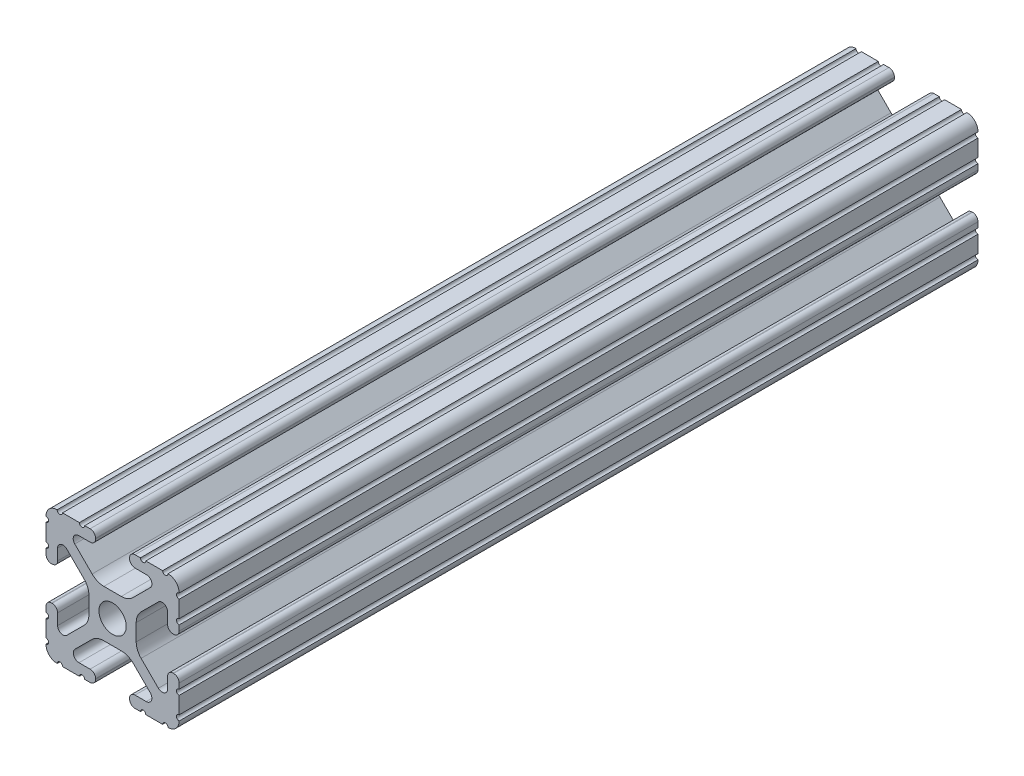
SolidWorks part; units mm, degrees
ref_plane "Front Plane" through (0, 0, 0) normal (0, 0, 1) x (1, 0, 0)
ref_plane "Top Plane" through (0, 0, 0) normal (0, 1, 0) x (1, 0, 0)
ref_plane "Right Plane" through (0, 0, 0) normal (1, 0, 0) x (0, 0, -1)
sketch "Sketch1" plane through (0, 0, 0) normal (0, 0, 1) x (1, 0, 0)
  line L88 (-7.1797, -8.6452) -> (-3.9523, -5.4237)
  line L89 (-1.7093, -4.4958) -> (1.7093, -4.4958)
  line L90 (3.9523, -5.4237) -> (7.1797, -8.6452)
  line L91 (6.4164, -10.4902) -> (4.2875, -10.4902)
  line L92 (3.2385, -11.5392) -> (3.2385, -11.651)
  line L93 (4.2875, -12.7) -> (5.3171, -12.7)
  line L94 (6.3331, -12.7) -> (9.5504, -12.7)
  line L95 (12.7, -9.5504) -> (12.7, -6.3331)
  line L96 (12.7, -5.3171) -> (12.7, -4.2875)
  line L97 (11.651, -3.2385) -> (11.5392, -3.2385)
  line L98 (10.4902, -4.2875) -> (10.4902, -6.4021)
  line L99 (8.7371, -7.1294) -> (5.441, -3.8408)
  line L100 (4.5085, -1.5932) -> (4.5085, 1.5932)
  line L101 (5.441, 3.8408) -> (8.7371, 7.1294)
  line L102 (10.4902, 6.4021) -> (10.4902, 4.2875)
  line L103 (11.5392, 3.2385) -> (11.651, 3.2385)
  line L104 (12.7, 4.2875) -> (12.7, 5.3171)
  line L105 (12.7, 6.3331) -> (12.7, 9.5504)
  line L106 (9.5504, 12.7) -> (6.3331, 12.7)
  line L107 (5.3171, 12.7) -> (4.2875, 12.7)
  line L108 (3.2385, 11.651) -> (3.2385, 11.5392)
  line L109 (4.2875, 10.4902) -> (6.4768, 10.4902)
  line L110 (7.207, 8.7244) -> (3.8983, 5.4232)
  line L111 (1.6558, 4.4958) -> (-1.6558, 4.4958)
  line L112 (-3.8983, 5.4232) -> (-7.207, 8.7244)
  line L113 (-6.4768, 10.4902) -> (-4.2875, 10.4902)
  line L114 (-3.2385, 11.5392) -> (-3.2385, 11.651)
  line L115 (-4.2875, 12.7) -> (-5.3171, 12.7)
  line L116 (-6.3331, 12.7) -> (-9.5504, 12.7)
  line L117 (-12.7, 9.5504) -> (-12.7, 6.3331)
  line L118 (-12.7, 5.3171) -> (-12.7, 4.2875)
  line L119 (-11.651, 3.2385) -> (-11.5392, 3.2385)
  line L120 (-10.4902, 4.2875) -> (-10.4902, 6.4021)
  line L121 (-8.7371, 7.1294) -> (-5.441, 3.8408)
  line L122 (-4.5085, 1.5932) -> (-4.5085, -1.5932)
  line L123 (-5.441, -3.8408) -> (-8.7371, -7.1294)
  line L124 (-10.4902, -6.4021) -> (-10.4902, -4.2875)
  line L125 (-11.5392, -3.2385) -> (-11.651, -3.2385)
  line L126 (-12.7, -4.2875) -> (-12.7, -5.3171)
  line L127 (-12.7, -6.3331) -> (-12.7, -9.5504)
  line L128 (-9.5504, -12.7) -> (-6.3331, -12.7)
  line L129 (-5.3171, -12.7) -> (-4.2875, -12.7)
  line L130 (-3.2385, -11.651) -> (-3.2385, -11.5392)
  line L131 (-4.2875, -10.4902) -> (-6.4164, -10.4902)
  circle A1 centre (0, 0) radius 2.6035
  arc A104 (-7.1797, -8.6452) -> (-6.4164, -10.4902) centre (-6.4164, -9.4098) ccw
  arc A105 (-1.7093, -4.4958) -> (-3.9523, -5.4237) centre (-1.7093, -7.6708) ccw
  arc A106 (3.9523, -5.4237) -> (1.7093, -4.4958) centre (1.7093, -7.6708) ccw
  arc A107 (6.4164, -10.4902) -> (7.1797, -8.6452) centre (6.4164, -9.4098) ccw
  arc A108 (4.2875, -10.4902) -> (3.2385, -11.5392) centre (4.2875, -11.5392) ccw
  arc A109 (3.2385, -11.651) -> (4.2875, -12.7) centre (4.2875, -11.651) ccw
  arc A110 (6.3331, -12.7) -> (5.3171, -12.7) centre (5.8251, -12.7) ccw
  arc A111 (10.5664, -12.6998) -> (9.5504, -12.7) centre (10.0584, -12.7) ccw
  arc A112 (10.5664, -12.6998) -> (12.6998, -10.5664) centre (10.5918, -10.5918) ccw
  arc A113 (12.7, -9.5504) -> (12.6998, -10.5664) centre (12.7, -10.0584) ccw
  arc A114 (12.7, -5.3171) -> (12.7, -6.3331) centre (12.7, -5.8251) ccw
  arc A115 (12.7, -4.2875) -> (11.651, -3.2385) centre (11.651, -4.2875) ccw
  arc A116 (11.5392, -3.2385) -> (10.4902, -4.2875) centre (11.5392, -4.2875) ccw
  arc A117 (8.7371, -7.1294) -> (10.4902, -6.4021) centre (9.4628, -6.4021) ccw
  arc A118 (4.5085, -1.5932) -> (5.441, -3.8408) centre (7.6835, -1.5932) ccw
  arc A119 (5.441, 3.8408) -> (4.5085, 1.5932) centre (7.6835, 1.5932) ccw
  arc A120 (10.4902, 6.4021) -> (8.7371, 7.1294) centre (9.4628, 6.4021) ccw
  arc A121 (10.4902, 4.2875) -> (11.5392, 3.2385) centre (11.5392, 4.2875) ccw
  arc A122 (11.651, 3.2385) -> (12.7, 4.2875) centre (11.651, 4.2875) ccw
  arc A123 (12.7, 6.3331) -> (12.7, 5.3171) centre (12.7, 5.8251) ccw
  arc A124 (12.6998, 10.5664) -> (12.7, 9.5504) centre (12.7, 10.0584) ccw
  arc A125 (12.6998, 10.5664) -> (10.5664, 12.6998) centre (10.5918, 10.5918) ccw
  arc A126 (9.5504, 12.7) -> (10.5664, 12.6998) centre (10.0584, 12.7) ccw
  arc A127 (5.3171, 12.7) -> (6.3331, 12.7) centre (5.8251, 12.7) ccw
  arc A128 (4.2875, 12.7) -> (3.2385, 11.651) centre (4.2875, 11.651) ccw
  arc A129 (3.2385, 11.5392) -> (4.2875, 10.4902) centre (4.2875, 11.5392) ccw
  arc A130 (7.207, 8.7244) -> (6.4768, 10.4902) centre (6.4768, 9.4563) ccw
  arc A131 (1.6558, 4.4958) -> (3.8983, 5.4232) centre (1.6558, 7.6708) ccw
  arc A132 (-3.8983, 5.4232) -> (-1.6558, 4.4958) centre (-1.6558, 7.6708) ccw
  arc A133 (-6.4768, 10.4902) -> (-7.207, 8.7244) centre (-6.4768, 9.4563) ccw
  arc A134 (-4.2875, 10.4902) -> (-3.2385, 11.5392) centre (-4.2875, 11.5392) ccw
  arc A135 (-3.2385, 11.651) -> (-4.2875, 12.7) centre (-4.2875, 11.651) ccw
  arc A136 (-6.3331, 12.7) -> (-5.3171, 12.7) centre (-5.8251, 12.7) ccw
  arc A137 (-10.5664, 12.6998) -> (-9.5504, 12.7) centre (-10.0584, 12.7) ccw
  arc A138 (-10.5664, 12.6998) -> (-12.6998, 10.5664) centre (-10.5918, 10.5918) ccw
  arc A139 (-12.7, 9.5504) -> (-12.6998, 10.5664) centre (-12.7, 10.0584) ccw
  arc A140 (-12.7, 5.3171) -> (-12.7, 6.3331) centre (-12.7, 5.8251) ccw
  arc A141 (-12.7, 4.2875) -> (-11.651, 3.2385) centre (-11.651, 4.2875) ccw
  arc A142 (-11.5392, 3.2385) -> (-10.4902, 4.2875) centre (-11.5392, 4.2875) ccw
  arc A143 (-8.7371, 7.1294) -> (-10.4902, 6.4021) centre (-9.4628, 6.4021) ccw
  arc A144 (-4.5085, 1.5932) -> (-5.441, 3.8408) centre (-7.6835, 1.5932) ccw
  arc A145 (-5.441, -3.8408) -> (-4.5085, -1.5932) centre (-7.6835, -1.5932) ccw
  arc A146 (-10.4902, -6.4021) -> (-8.7371, -7.1294) centre (-9.4628, -6.4021) ccw
  arc A147 (-10.4902, -4.2875) -> (-11.5392, -3.2385) centre (-11.5392, -4.2875) ccw
  arc A148 (-11.651, -3.2385) -> (-12.7, -4.2875) centre (-11.651, -4.2875) ccw
  arc A149 (-12.7, -6.3331) -> (-12.7, -5.3171) centre (-12.7, -5.8251) ccw
  arc A150 (-12.6998, -10.5664) -> (-12.7, -9.5504) centre (-12.7, -10.0584) ccw
  arc A151 (-12.6998, -10.5664) -> (-10.5664, -12.6998) centre (-10.5918, -10.5918) ccw
  arc A152 (-9.5504, -12.7) -> (-10.5664, -12.6998) centre (-10.0584, -12.7) ccw
  arc A153 (-5.3171, -12.7) -> (-6.3331, -12.7) centre (-5.8251, -12.7) ccw
  arc A154 (-4.2875, -12.7) -> (-3.2385, -11.651) centre (-4.2875, -11.651) ccw
  arc A155 (-3.2385, -11.5392) -> (-4.2875, -10.4902) centre (-4.2875, -11.5392) ccw
extrude "Boss-Extrude1" add sketch "Sketch1" along normal mid plane 609.6
sketch "Sketch2" plane through (0, 0, 304.8) normal (0, 0, 1) x (1, 0, 0)
  circle A0 centre (0, 0) radius 37.7136
extrude "Cut-Extrude1" cut sketch "Sketch2" against normal blind 203.2
sketch "Sketch4" plane through (0, 0, 101.6) normal (0, 0, 1) x (1, 0, 0)
  circle A0 centre (0, 0) radius 34.5291
extrude "Cut-Extrude3" cut sketch "Sketch4" against normal blind 254
sketch "Sketch5" plane through (4.5085, 0, 0) normal (1, 0, 0) x (0, 0, -1)
  line L0 (228.6, -1.5932) -> (228.6, 1.5932) construction
  line L1 (152.4, -1.5932) -> (304.8, -1.5932) construction
  line L2 (152.4, 1.5932) -> (304.8, 1.5932) construction
  circle A0 centre (228.6, 0) radius 0.254
extrude "Cut-Extrude4" cut sketch "Sketch5" against normal blind 254
ref_axis "Axis2" through (2.5767, 0, -228.6) along (1, 0, 0)
